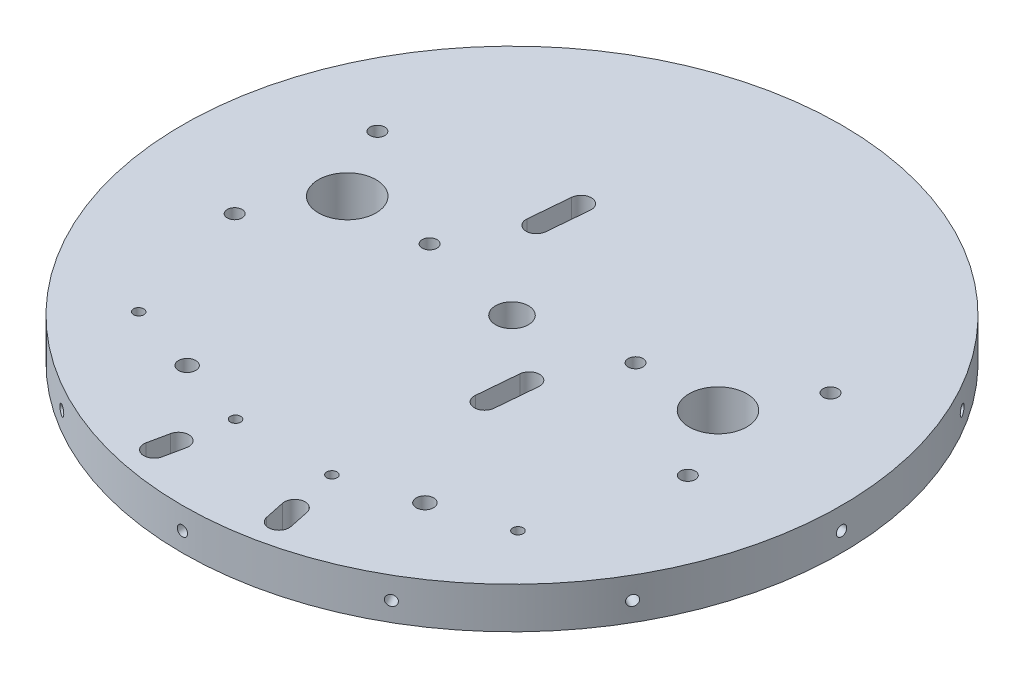
SolidWorks part; units mm, degrees
material "6061 Alloy"
ref_plane "Front Plane" through (0, 0, 0) normal (0, 0, 1) x (1, 0, 0)
ref_plane "Top Plane" through (0, 0, 0) normal (0, 1, 0) x (1, 0, 0)
ref_plane "Right Plane" through (0, 0, 0) normal (1, 0, 0) x (0, 0, -1)
sketch "Sketch1" plane through (0, 0, 0) normal (0, 1, 0) x (1, 0, 0)
  circle A0 centre (0, 0) radius 80
extrude "Boss-Extrude1" add sketch "Sketch1" against normal blind 10
sketch "Sketch3" plane through (0, 0, 0) normal (0, 1, 0) x (1, 0, 0)
  circle A0 centre (0, 0) radius 4
extrude "Cut-Extrude1" cut sketch "Sketch3" against normal blind 12
sketch "Sketch4" plane through (0, 0, 0) normal (0, 1, 0) x (1, 0, 0)
  line L1 (45, 5) -> (-45, 5)
  circle A2 centre (-45, 5) radius 7
  circle A3 centre (45, 5) radius 7
  point P5 (0, 0)
extrude "Cut-Extrude2" cut sketch "Sketch4" against normal blind 12 contours A2 | A3 region at (-51.802, 0, -5) region at (45, 0, -11.802)
ref_plane "Plane1" through (0, 0, 80) normal (0, 0, 1) x (1, 0, 0)
sketch "Sketch5" plane through (0, 0, 80) normal (0, 0, 1) x (1, 0, 0)
  circle A0 centre (0, -5.3239) radius 1.25
extrude "Cut-Extrude3" cut sketch "Sketch5" against normal blind 15
pattern_circular "CirPattern1" count 12 over 360 about axis through (0, 0, 0) along (0, 1, 0) of "Cut-Extrude3"
sketch "Sketch6" plane through (0, 0, 0) normal (0, 1, 0) x (1, 0, 0)
  line L2 (-45, 5) -> (-25, 5) construction
  line L3 (45, 5) -> (25, 5) construction
  circle A2 centre (-25, 5) radius 1.8
  circle A3 centre (25, 5) radius 1.8
  circle A4 centre (-55, 22.3205) radius 1.8
  circle A5 centre (-55, -12.3205) radius 1.8
  circle A6 centre (55, 22.3205) radius 1.8
  circle A7 centre (55, -12.3205) radius 1.8
  point P7 (-45, 5)
  point P18 (45, 5)
  dimension "D1" = 3
  dimension "D2" = 3
extrude "Cut-Extrude4" cut sketch "Sketch6" against normal up to next contours A2 | A3 | A4 | A5 | A7 | A6 region at (-25, 0, -5) region at (25, 0, -5) region at (-55, 0, -22.3205) region at (-55, 0, 12.3205) region at (55, 0, -22.3205) region at (55, 0, 12.3205)
sketch "Sketch9" plane through (0, -10, 0) normal (0, -1, 0) x (1, 0, 0)
  circle A0 centre (0, 0) radius 12.5
extrude "Cut-Extrude5" cut sketch "Sketch9" against normal blind 3
sketch "Sketch10" plane through (0, 0, 0) normal (0, 1, 0) x (1, 0, 0)
  line L0 (0, 0) -> (0, -80) construction
  line L1 (0, 0) -> (28.8675, -50)
  line L2 (0, 0) -> (-28.8675, -50)
  line L4 (-28.8675, -50) -> (28.8675, -50)
  circle A0 centre (0, 0) radius 80 construction
  circle A4 centre (-28.8675, -50) radius 2.1
  circle A5 centre (28.8675, -50) radius 2.1
  point P12 (17.3205, -60)
  dimension "D1" = 30
  dimension "D2" = 30
extrude "Cut-Extrude6" cut sketch "Sketch10" against normal up to next contours L1 A5 L4 | L4 A5 L1 | A4 region at (29.0991, 0, 50.1337) region at (27.7097, 0, 49.3315)
sketch "Sketch11" plane through (0, 0, 0) normal (0, 1, 0) x (1, 0, 0)
  line L0 (0, 0) -> (0, -80) construction
  line L1 (28.8675, -50) -> (0, -59.1019) construction
  line L2 (0, -59.1019) -> (-28.8675, -50) construction
  circle A0 centre (0, 0) radius 80 construction
  circle A1 centre (11.7006, -55.4127) radius 1.25
  circle A2 centre (-11.7006, -55.4127) radius 1.25
  circle A3 centre (46.0344, -44.5873) radius 1.25
  circle A4 centre (-46.0344, -44.5873) radius 1.25
  point P20 (28.8675, -50)
  point P22 (-28.8675, -50)
  dimension "D2" = 18
  dimension "D3" = 18
  dimension "D1" = 145
  dimension "D4" = 2
  dimension "D5" = 2
extrude "Cut-Extrude7" cut sketch "Sketch11" against normal up to next
sketch "Sketch12" plane through (0, 0, 0) normal (0, 1, 0) x (1, 0, 0)
  line L0 (0, 0) -> (11.7006, -55.4127) construction
  line L1 (11.7006, -55.4127) -> (16.5279, -78.2741) construction
  line L2 (0, 0) -> (-11.7006, -55.4127) construction
  line L3 (-11.7006, -55.4127) -> (-16.5279, -78.2741) construction
  line L4 (16.5603, -66.3269) -> (17.5933, -71.219)
  line L5 (12.7012, -72.252) -> (11.6682, -67.3599)
  line L6 (-11.6682, -67.3599) -> (-12.7012, -72.252)
  line L7 (-16.5603, -66.3269) -> (-17.5933, -71.219)
  circle A0 centre (0, 0) radius 80 construction
  arc A1 (16.5603, -66.3269) -> (11.6682, -67.3599) centre (14.1142, -66.8434) ccw
  arc A2 (-11.6682, -67.3599) -> (-16.5603, -66.3269) centre (-14.1142, -66.8434) ccw
  arc A3 (-17.5933, -71.219) -> (-12.7012, -72.252) centre (-15.1472, -71.7355) ccw
  arc A4 (12.7012, -72.252) -> (17.5933, -71.219) centre (15.1472, -71.7355) ccw
  dimension "D1" = 5
  dimension "D2" = 5
extrude "Cut-Extrude8" cut sketch "Sketch12" against normal up to next
sketch "Sketch13" plane through (0, 0, 0) normal (0, 1, 0) x (1, 0, 0)
  line L0 (28.8675, -50) -> (0, 0) construction
  line L1 (0, 0) -> (-40, 69.282) construction
  line L2 (33.1976, -47.5) -> (4.3301, 2.5) construction
  line L3 (18.0385, -14.28) -> (17.6027, -19.2609)
  line L4 (13.0575, -13.8442) -> (12.6218, -18.8252)
  line L5 (-17.8099, 0.4442) -> (-13.1901, 53.2494) construction
  line L6 (9.2515, -86.0316) -> (21.4088, 52.9265) construction
  line L7 (-12.7916, 29.1194) -> (-13.2274, 24.1384)
  line L8 (-17.7726, 29.5552) -> (-18.2084, 24.5742)
  line L9 (-12.5737, 31.6099) -> (-13.4453, 21.6479)
  line L10 (-17.5547, 32.0457) -> (-18.4263, 22.0837)
  line L11 (18.2564, -11.7895) -> (17.3848, -21.7514)
  line L12 (13.2754, -11.3537) -> (12.4039, -21.3156)
  circle A0 centre (0, 0) radius 80 construction
  arc A11 (-12.5737, 31.6099) -> (-17.5547, 32.0457) centre (-15.0642, 31.8278) ccw
  arc A12 (-18.4263, 22.0837) -> (-13.4453, 21.6479) centre (-15.9358, 21.8658) ccw
  arc A14 (18.2564, -11.7895) -> (13.2754, -11.3537) centre (15.7659, -11.5716) ccw
  arc A15 (-13.4521, 23.2998) -> (-13.2274, 24.1384) centre (-15.7179, 24.3563) ccw
  arc A16 (12.4039, -21.3156) -> (17.3848, -21.7514) centre (14.8943, -21.5335) ccw
  point P16 (-15.5, 26.8468)
  point P19 (15.3301, -16.5526)
  point P22 (-15.5, 26.8468)
  point P25 (15.3301, -16.5526)
  point P26 (15.3301, -16.5526)
  dimension "D2" = 35
  dimension "D3" = 35
  dimension "D1" = 5
extrude "Cut-Extrude10" cut sketch "Sketch13" against normal up to next contours L10 A12 L9 L7 A11 L8 | L12 A16 L11 L3 A14 L4 region at (15.3301, 0, 16.5526) region at (-15.5, 0, -26.8468)
